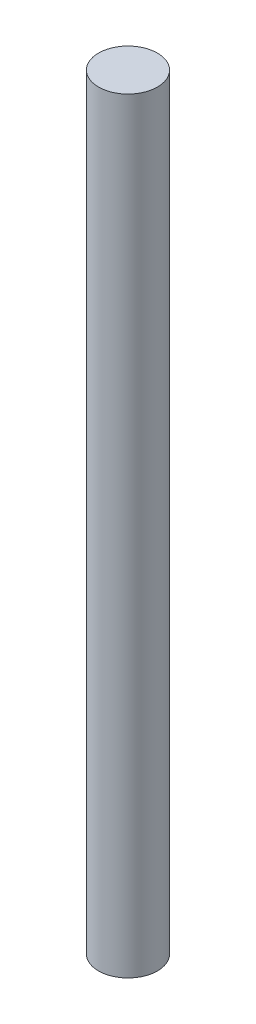
SolidWorks part; units mm, degrees
material "PBT General Purpose"
ref_plane "Front Plane" through (0, 0, 0) normal (0, 0, 1) x (1, 0, 0)
ref_plane "Top Plane" through (0, 0, 0) normal (0, 1, 0) x (1, 0, 0)
ref_plane "Right Plane" through (0, 0, 0) normal (1, 0, 0) x (0, 0, -1)
sketch "Sketch1" plane through (0, 0, 0) normal (0, 1, 0) x (1, 0, 0)
  circle A0 centre (0, 0) radius 2.5
  dimension "D1" = 5
extrude "Boss-Extrude1" add sketch "Sketch1" along normal blind 65
